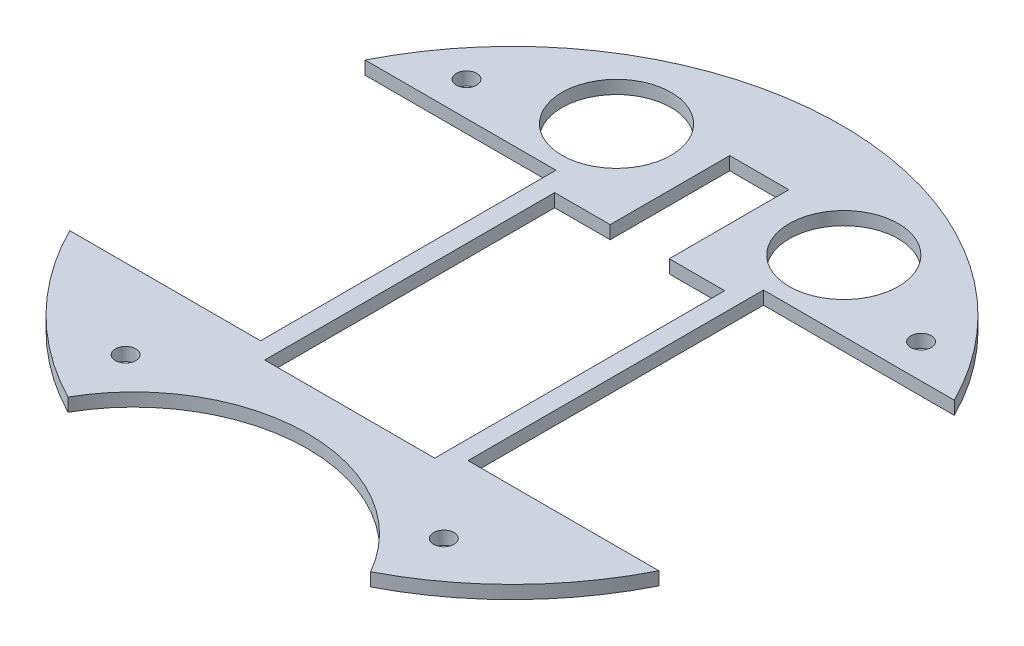
SolidWorks part; units mm, degrees
material "Acrylic (Medium-high impact)"
ref_plane "Front Plane" through (0, 0, 0) normal (0, 0, 1) x (1, 0, 0)
ref_plane "Top Plane" through (0, 0, 0) normal (0, 1, 0) x (1, 0, 0)
ref_plane "Right Plane" through (0, 0, 0) normal (1, 0, 0) x (0, 0, -1)
sketch "Sketch1" plane through (0, 0, 0) normal (0, 1, 0) x (1, 0, 0)
  line L0 (0, -83.2398) -> (-33.2911, -64.4046) construction
  line L1 (0, -83.2398) -> (0, 0) construction
  arc A0 (33.2911, -64.4046) -> (-33.2911, -64.4046) centre (0, 0) ccw
  arc A1 (33.2911, -64.4046) -> (-33.2911, -64.4046) centre (0, -83.2398) ccw
  dimension "D1" = 145
  dimension "D2" = 76.5
  dimension "D3" = 60.5
extrude "Boss-Extrude1" add sketch "Sketch1" along normal blind 2.9
sketch "solenoid placement" plane through (0, 2.9, 0) normal (0, 1, 0) x (1, 0, 0)
  line L4 (-18.7, -35.7) -> (18.7, -35.7)
  line L5 (18.7, -35.7) -> (18.7, 28.1)
  line L6 (18.7, 28.1) -> (-18.7, 28.1)
  line L7 (-18.7, 28.1) -> (-18.7, -35.7)
  line L8 (-18.7, -35.7) -> (18.7, -35.7)
  line L9 (18.7, -35.7) -> (18.7, 28.1)
  line L10 (18.7, 28.1) -> (-18.7, 28.1)
  line L11 (-18.7, 28.1) -> (-18.7, -35.7)
  circle A1 centre (0, 0) radius 72.5 construction
  arc A2 (33.2911, -64.4046) -> (-33.2911, -64.4046) centre (0, 0) ccw construction
  dimension "D1" = 0
extrude "Cut-Extrude1" cut sketch "solenoid placement" against normal through all
sketch "Sketch3" plane through (0, 2.9, 0) normal (0, 1, 0) x (1, 0, 0)
  line L4 (-34.63, -32.5) -> (-22.83, -32.5)
  line L5 (-22.83, -32.5) -> (-22.83, 32.5)
  line L6 (-22.83, 32.5) -> (-64.8074, 32.5)
  line L7 (-64.8074, -32.5) -> (-34.63, -32.5)
  line L8 (-34.63, -32.5) -> (-22.83, -32.5)
  line L9 (-22.83, -32.5) -> (-22.83, 32.5)
  line L10 (-22.83, 32.5) -> (-64.8074, 32.5)
  line L11 (-64.8074, -32.5) -> (-34.63, -32.5)
  line L12 (34.63, -32.5) -> (64.8074, -32.5)
  line L13 (64.8074, 32.5) -> (22.83, 32.5)
  line L14 (22.83, 32.5) -> (22.83, -32.5)
  line L15 (22.83, -32.5) -> (34.63, -32.5)
  line L16 (34.63, -32.5) -> (64.8074, -32.5)
  line L17 (64.8074, 32.5) -> (22.83, 32.5)
  line L18 (22.83, 32.5) -> (22.83, -32.5)
  line L19 (22.83, -32.5) -> (34.63, -32.5)
  arc A2 (-64.8074, 32.5) -> (-64.8074, -32.5) centre (0, 0) ccw
  arc A3 (-64.8074, 32.5) -> (-64.8074, -32.5) centre (0, 0) ccw
  arc A4 (64.8074, -32.5) -> (64.8074, 32.5) centre (0, 0) ccw
  arc A5 (64.8074, -32.5) -> (64.8074, 32.5) centre (0, 0) ccw
  dimension "D2" = 0
  dimension "D1" = 0
extrude "Cut-Extrude3" cut sketch "Sketch3" against normal through all
sketch "Sketch4" plane through (0, 2.9, 0) normal (0, 1, 0) x (1, 0, 0)
  line L0 (18.7, 28.1) -> (-18.7, 28.1) construction
  line L1 (-6.5, 28.1) -> (6.5, 28.1)
  line L2 (-6.5, 28.1) -> (-6.5, 54.4)
  line L3 (6.5, 54.4) -> (-6.5, 54.4) construction
  line L4 (6.5, 28.1) -> (6.5, 54.4)
  line L5 (6.5, 54.4) -> (-6.5, 54.4)
  point P6 (0, 28.1)
extrude "Cut-Extrude4" cut sketch "Sketch4" against normal through all
sketch "Sketch5" plane through (0, 2.9, 0) normal (0, 1, 0) x (1, 0, 0)
  circle A2 centre (-25, 48) radius 12
  circle A3 centre (-25, 48) radius 12
  circle A4 centre (25, 48) radius 12
  circle A21 centre (25, 48) radius 12
  dimension "D1" = 0
  dimension "D2" = 0
extrude "Cut-Extrude5" cut sketch "Sketch5" against normal through all
sketch "Sketch6" plane through (0, 2.9, 0) normal (0, 1, 0) x (1, 0, 0)
  circle A1 centre (35, -50) radius 2.25
  circle A2 centre (35, -50) radius 2.25
  circle A3 centre (-35, -50) radius 2.25
  circle A4 centre (-35, -50) radius 2.25
  circle A5 centre (-50, 40) radius 2.25
  circle A6 centre (-50, 40) radius 2.25
  circle A7 centre (50, 40) radius 2.25
  circle A8 centre (50, 40) radius 2.25
  dimension "D1" = 0
  dimension "D2" = 0
  dimension "D3" = 0
  dimension "D4" = 0
extrude "Cut-Extrude6" cut sketch "Sketch6" against normal through all
equation "\"smallPulleyTeeth\"= 15"
equation "\"largePulleyTeeth\"= 30"
equation "\"eighthThick\"= 2.9mm"
equation "\"sixteenthThick\" = 1.7mm"
equation "\"quarterThick\"=5.9mm"
equation "\"OD\" = 145mm"
equation "\"puckAngle\" = 60.5deg"
equation "\"D1@Sketch1\"=\"OD\""
equation "\"puckDiam\" = 76.5mm"
equation "\"D2@Sketch1\"=\"puckDiam\""
equation "\"D3@Sketch1\"=\"puckAngle\""
equation "\"D1@Boss-Extrude1\"=\"eighthThick\""
equation "\"axlePress\" = 5.9mm"
equation "\"press\" = 0.2mm"
equation "\"wheelClear\" = 0.3mm"
equation "\"10-32clear\" = 4.5mm"
equation "\"6-32clear\" = 3.3mm"
equation "\"8-32clear\" = 4.0mm"
equation "\"wheelHeight\" = 22mm"
equation "\"wheelWell\" = 65mm"
